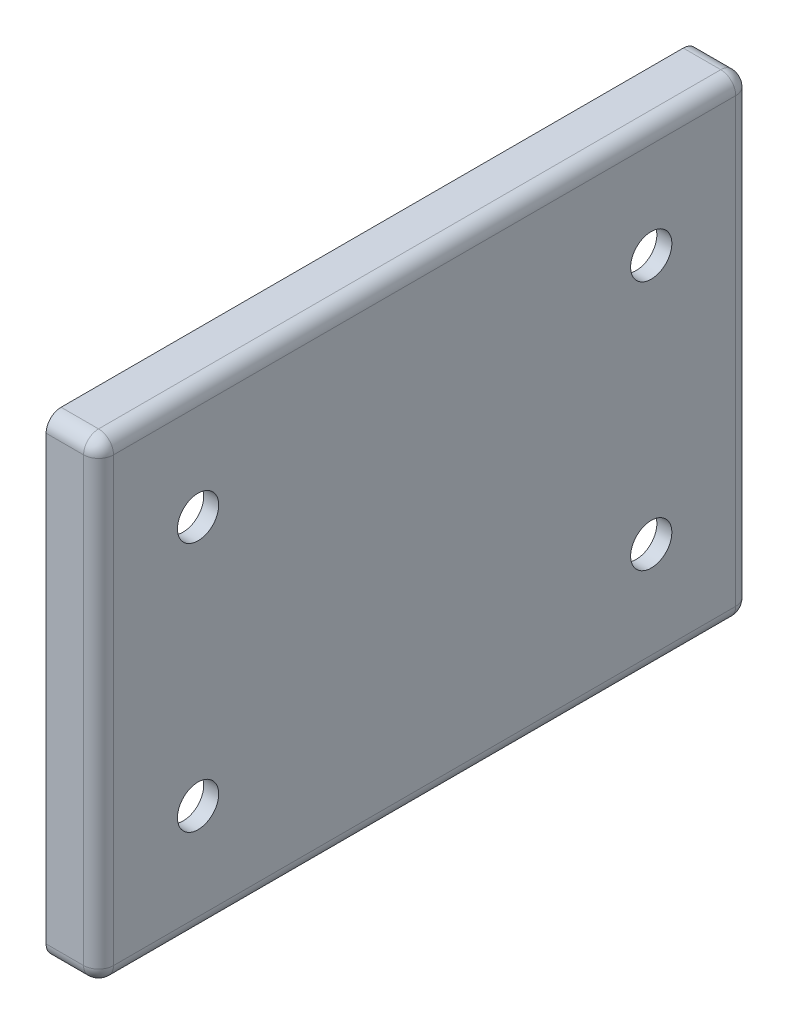
SolidWorks part; units mm, degrees
ref_plane "前视基准面" through (0, 0, 0) normal (0, 0, 1) x (1, 0, 0)
ref_plane "上视基准面" through (0, 0, 0) normal (0, 1, 0) x (1, 0, 0)
ref_plane "右视基准面" through (0, 0, 0) normal (1, 0, 0) x (0, 0, -1)
sketch "草图1" plane through (0, 0, 0) normal (1, 0, 0) x (0, 0, -1)
  line L1 (-37.5961, 46.5132) -> (45.4039, 46.5132)
  line L2 (-37.5961, 46.5132) -> (-37.5961, -12.4868)
  line L3 (-37.5961, -12.4868) -> (45.4039, -12.4868)
  line L4 (45.4039, 46.5132) -> (45.4039, -12.4868)
  line L5 (-39.5961, 48.5132) -> (47.4039, 48.5132)
  line L6 (-39.5961, 48.5132) -> (-39.5961, -14.4868)
  line L7 (-39.5961, -14.4868) -> (47.4039, -14.4868)
  line L8 (47.4039, 48.5132) -> (47.4039, -14.4868)
  dimension "D1" = 83
  dimension "D2" = 59
  dimension "D3" = 2
  dimension "D4" = 2
  dimension "D5" = 2
  dimension "D6" = 2
extrude "凸台-拉伸1" add sketch "草图1" along normal blind 5
sketch "草图2" plane through (5, 0, 0) normal (1, 0, 0) x (0, 0, -1)
  line L1 (-39.5961, 48.5132) -> (47.4039, 48.5132)
  line L2 (-39.5961, 48.5132) -> (-39.5961, -14.4868)
  line L3 (-39.5961, -14.4868) -> (47.4039, -14.4868)
  line L4 (47.4039, 48.5132) -> (47.4039, -14.4868)
extrude "凸台-拉伸2" add sketch "草图2" along normal blind 2
sketch "草图3" plane through (0, 0, -47.4039) normal (0, 0, -1) x (-1, 0, 0)
  line L1 (-5.0451, -4.4807) -> (-2.2805, -4.4807)
  line L2 (-5.0451, -4.4807) -> (-5.0451, -9.1322)
  line L3 (-5.0451, -9.1322) -> (-2.2805, -9.1322)
  line L4 (-2.2805, -4.4807) -> (-2.2805, -9.1322)
extrude "切除-拉伸1" cut sketch "草图3" against normal blind 2
fillet "圆角1" radius 2 8 edges at (3.5, 48.5132, -47.4039) (3.5, -14.4868, -47.4039) (3.5, -14.4868, 39.5961) (3.5, 48.5132, 39.5961) (7, 48.5132, -3.9039) (7, 17.0132, -47.4039) (7, -14.4868, -3.9039) (7, 17.0132, 39.5961)
sketch "草图4" plane through (5, 0, 0) normal (-1, 0, 0) x (0, 0, 1)
  line L0 (37.5961, -12.4868) -> (-45.4039, -12.4868) construction
  line L1 (0, -8.581) -> (27.389, -8.581)
  line L2 (0, -8.581) -> (0, -12.4868)
  line L3 (0, -12.4868) -> (27.389, -12.4868)
  line L4 (27.389, -8.581) -> (27.389, -12.4868)
  line L5 (-45.4039, 46.5132) -> (37.5961, 46.5132) construction
  line L6 (-45.4039, 46.5132) -> (-31.6975, 46.5132)
  line L7 (-45.4039, 46.5132) -> (-45.4039, 42.0074)
  line L8 (-45.4039, 42.0074) -> (-31.6975, 42.0074)
  line L9 (-31.6975, 46.5132) -> (-31.6975, 42.0074)
  line L10 (26.4391, 46.5132) -> (37.5961, 46.5132)
  line L11 (26.4391, 46.5132) -> (26.4391, 43.6618)
  line L12 (26.4391, 43.6618) -> (37.5961, 43.6618)
  line L13 (37.5961, 46.5132) -> (37.5961, 43.6618)
  line L14 (37.5961, 46.5132) -> (37.5961, -12.4868) construction
  line L16 (37.5961, 38.8082) -> (34.487, 38.8082)
  line L17 (37.5961, 38.8082) -> (37.5961, -5.6817)
  line L18 (37.5961, -5.6817) -> (34.487, -5.6817)
  line L19 (34.487, 38.8082) -> (34.487, -5.6817)
extrude "凸台-拉伸3" add sketch "草图4" along normal blind 3.3
sketch "草图5" plane through (5, 0, 0) normal (-1, 0, 0) x (0, 0, 1)
  line L0 (-47.4039, 17.0132) -> (-33.1302, 17.0132) construction
  line L2 (-3.9039, 48.5132) -> (-3.9039, 32.5271) construction
  line L5 (-34.1311, 33.6989) -> (26.3234, 33.6989) construction
  line L6 (-34.1311, 33.6989) -> (-34.1311, 0.3274) construction
  line L7 (-34.1311, 0.3274) -> (26.3234, 0.3274) construction
  line L8 (26.3234, 33.6989) -> (26.3234, 0.3274) construction
  line L9 (-34.1311, 33.6989) -> (26.3234, 0.3274) construction
  line L10 (-34.1311, 0.3274) -> (26.3234, 33.6989) construction
  circle A0 centre (-34.1311, 33.6989) radius 2.75
  circle A1 centre (26.3234, 33.6989) radius 2.75
  circle A2 centre (-34.1311, 0.3274) radius 2.75
  circle A3 centre (26.3234, 0.3274) radius 2.75
  point P4 (-3.9039, 17.0132)
  dimension "D1" = 5.5
  dimension "D2" = 5.5
  dimension "D3" = 5.5
  dimension "D4" = 5.5
extrude "切除-拉伸2" cut sketch "草图5" against normal blind 10
